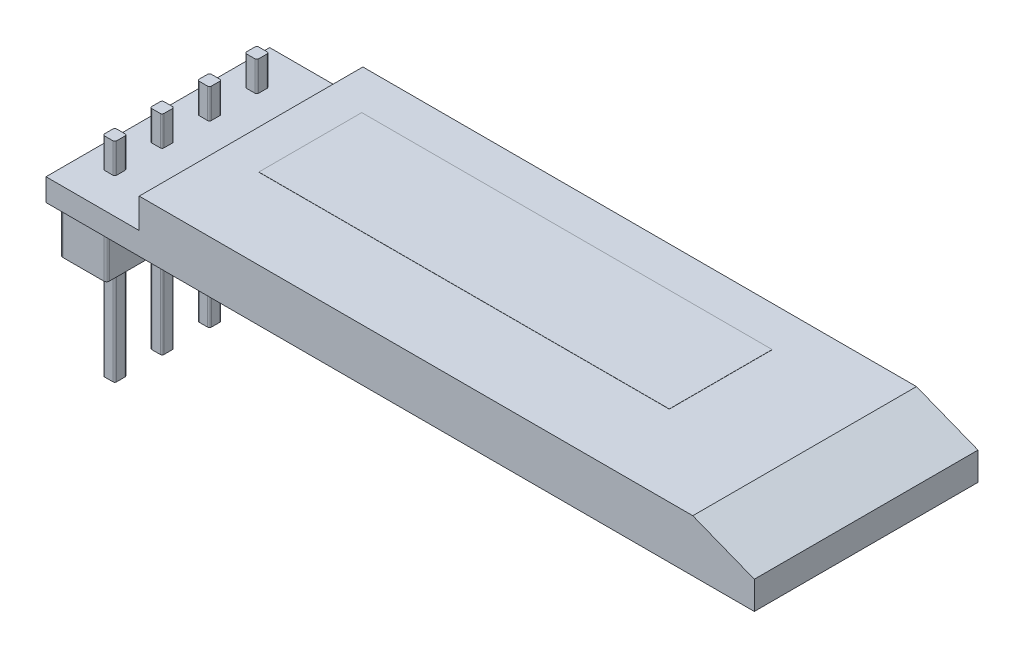
SolidWorks part; units mm, degrees
ref_plane "Спереди" through (0, 0, 0) normal (0, 0, 1) x (1, 0, 0)
ref_plane "Сверху" through (0, 0, 0) normal (0, 1, 0) x (1, 0, 0)
ref_plane "Справа" through (0, 0, 0) normal (1, 0, 0) x (0, 0, -1)
sketch "Основное" plane through (0, 0, 0) normal (0, 1, 0) x (1, 0, 0)
  line L0 (-14, 6) -> (-14, -6)
  line L1 (19, -6) -> (-19, -6)
  line L2 (19, -6) -> (19, 6)
  line L3 (19, 6) -> (-19, 6)
  line L4 (-19, -6) -> (-19, 6)
  line L5 (19, -6) -> (-19, 6) construction
  line L6 (19, 6) -> (-19, -6) construction
  line L7 (-17.5, 3.81) -> (-17.5, 0) construction
  line L8 (-16.4, -5.5) -> (-18.6, -5.5)
  line L9 (-16.25, -5.35) -> (-16.25, 5.35)
  line L10 (-16.4, 5.5) -> (-18.6, 5.5)
  line L11 (-18.75, -5.35) -> (-18.75, 5.35)
  line L12 (-16.25, -5.5) -> (-18.75, 5.5) construction
  line L13 (-16.25, 5.5) -> (-18.75, -5.5) construction
  line L14 (-17.275, 3.485) -> (-17.725, 3.485)
  line L15 (-17.175, 3.585) -> (-17.175, 4.035)
  line L16 (-17.275, 4.135) -> (-17.725, 4.135)
  line L17 (-17.825, 3.585) -> (-17.825, 4.035)
  line L18 (-17.175, 3.485) -> (-17.825, 4.135) construction
  line L19 (-17.175, 4.135) -> (-17.825, 3.485) construction
  line L20 (-17.275, 0.945) -> (-17.725, 0.945)
  line L21 (-17.175, 1.045) -> (-17.175, 1.495)
  line L22 (-17.275, 1.595) -> (-17.725, 1.595)
  line L23 (-17.825, 1.045) -> (-17.825, 1.495)
  line L24 (-17.175, 0.945) -> (-17.825, 1.595) construction
  line L25 (-17.175, 1.595) -> (-17.825, 0.945) construction
  line L26 (-17.275, -1.595) -> (-17.725, -1.595)
  line L27 (-17.175, -1.495) -> (-17.175, -1.045)
  line L28 (-17.275, -0.945) -> (-17.725, -0.945)
  line L29 (-17.825, -1.495) -> (-17.825, -1.045)
  line L30 (-17.175, -1.595) -> (-17.825, -0.945) construction
  line L31 (-17.175, -0.945) -> (-17.825, -1.595) construction
  line L32 (-17.275, -4.135) -> (-17.725, -4.135)
  line L33 (-17.175, -4.035) -> (-17.175, -3.585)
  line L34 (-17.275, -3.485) -> (-17.725, -3.485)
  line L35 (-17.825, -4.035) -> (-17.825, -3.585)
  line L36 (-17.175, -4.135) -> (-17.825, -3.485) construction
  line L37 (-17.175, -3.485) -> (-17.825, -4.135) construction
  arc A0 (-16.4, -5.5) -> (-16.25, -5.35) centre (-16.4, -5.35) ccw
  arc A1 (-18.6, -5.5) -> (-18.75, -5.35) centre (-18.6, -5.35) cw
  arc A2 (-18.6, 5.5) -> (-18.75, 5.35) centre (-18.6, 5.35) ccw
  arc A3 (-16.25, 5.35) -> (-16.4, 5.5) centre (-16.4, 5.35) ccw
  arc A4 (-17.725, 3.485) -> (-17.825, 3.585) centre (-17.725, 3.585) cw
  arc A5 (-17.275, 3.485) -> (-17.175, 3.585) centre (-17.275, 3.585) ccw
  arc A6 (-17.175, 4.035) -> (-17.275, 4.135) centre (-17.275, 4.035) ccw
  arc A7 (-17.725, 4.135) -> (-17.825, 4.035) centre (-17.725, 4.035) ccw
  arc A8 (-17.725, 0.945) -> (-17.825, 1.045) centre (-17.725, 1.045) cw
  arc A9 (-17.275, 0.945) -> (-17.175, 1.045) centre (-17.275, 1.045) ccw
  arc A10 (-17.175, 1.495) -> (-17.275, 1.595) centre (-17.275, 1.495) ccw
  arc A11 (-17.725, 1.595) -> (-17.825, 1.495) centre (-17.725, 1.495) ccw
  arc A12 (-17.725, -1.595) -> (-17.825, -1.495) centre (-17.725, -1.495) cw
  arc A13 (-17.275, -1.595) -> (-17.175, -1.495) centre (-17.275, -1.495) ccw
  arc A14 (-17.175, -1.045) -> (-17.275, -0.945) centre (-17.275, -1.045) ccw
  arc A15 (-17.725, -0.945) -> (-17.825, -1.045) centre (-17.725, -1.045) ccw
  arc A16 (-17.725, -4.135) -> (-17.825, -4.035) centre (-17.725, -4.035) cw
  arc A17 (-17.275, -4.135) -> (-17.175, -4.035) centre (-17.275, -4.035) ccw
  arc A18 (-17.175, -3.585) -> (-17.275, -3.485) centre (-17.275, -3.585) ccw
  arc A19 (-17.725, -3.485) -> (-17.825, -3.585) centre (-17.725, -3.585) ccw
  point P0 (0, 0)
  point P8 (-17.5, 0)
  point P9 (-17.5, 0)
  point P26 (-17.5, 3.81)
  point P47 (-17.5, 1.27)
  point P64 (-17.5, -1.27)
  point P81 (-17.5, -3.81)
  dimension "D6" = 11
  dimension "D4" = 0.15
  dimension "D9" = 0.1
  dimension "D1" = 12
  dimension "D2" = 38
  dimension "D3" = 33
  dimension "D5" = 2.5
  dimension "D7" = 0.5
  dimension "D8" = 4
  dimension "D10" = 2.19
  dimension "D11" = 1.5
extrude "Бобышка-Вытянуть1" add sketch "Основное" along normal blind 2.8 contours L2 L3 L0 L1 region at (2.5, 0, 0)
extrude "Бобышка-Вытянуть2" add sketch "Эскиз1<3>" along normal blind 1.2 contours L4 L1 L0 L3 A3 L9 A0 L8 A1 L11 A2 L10 region at (-15.6549, 0, 0)
sketch "Эскиз1<3>" plane through (0, 0, 0) normal (0, 1, 0) x (1, 0, 0) same geometry as "Основное"
extrude "Бобышка-Вытянуть3" add sketch "Эскиз1<4>" along normal blind 1.2 and the other way blind 2.6 contours L9 A3 L10 A2 L11 A1 L8 A0 A19 L34 A18 L33 A17 L32 A16 L35 A15 L28 A14 L27 A13 L26 A12 L29 A11 L22 A10 L21 A9 L20 A8 L23 A7 L16 A6 L15 A5 L14 A4 L17 region at (-17.5, 0, 0)
sketch "Эскиз1<4>" plane through (0, 0, 0) normal (0, 1, 0) x (1, 0, 0) same geometry as "Основное"
extrude "Бобышка-Вытянуть4" add sketch "Эскиз1<6>" along normal blind 2.8 and the other way blind 8.4 separate body contours L17 A7 L16 A6 L15 A5 L14 A4 | L23 A11 L22 A10 L21 A9 L20 A8 | L29 A15 L28 A14 L27 A13 L26 A12 | L35 A19 L34 A18 L33 A17 L32 A16
sketch "Эскиз1<6>" plane through (0, 0, 0) normal (0, 1, 0) x (1, 0, 0) same geometry as "Основное"
chamfer "Фаска2" distance 1.3 distance2 3.3 1 edges at (19, 2.8, 0) first distance on face at (19, 1.4, 0)
sketch "Дисплей" plane through (0, 2.8, 0) normal (0, 1, 0) x (1, 0, 0)
  line L1 (-11.9, 3.84) -> (10.1171, 3.84)
  line L2 (-11.9, 3.84) -> (-11.9, -1.68)
  line L3 (-11.9, -1.68) -> (10.1171, -1.68)
  line L4 (10.1171, 3.84) -> (10.1171, -1.68)
  line L7 (-19, -6) -> (-19, 6) construction
  dimension "D1" = 2.16
  dimension "D2" = 7.1
  dimension "D3" = 5.52
  dimension "D4" = 22.0171
extrude "Бобышка-Вытянуть5" add sketch "Дисплей" along normal blind 0.01
